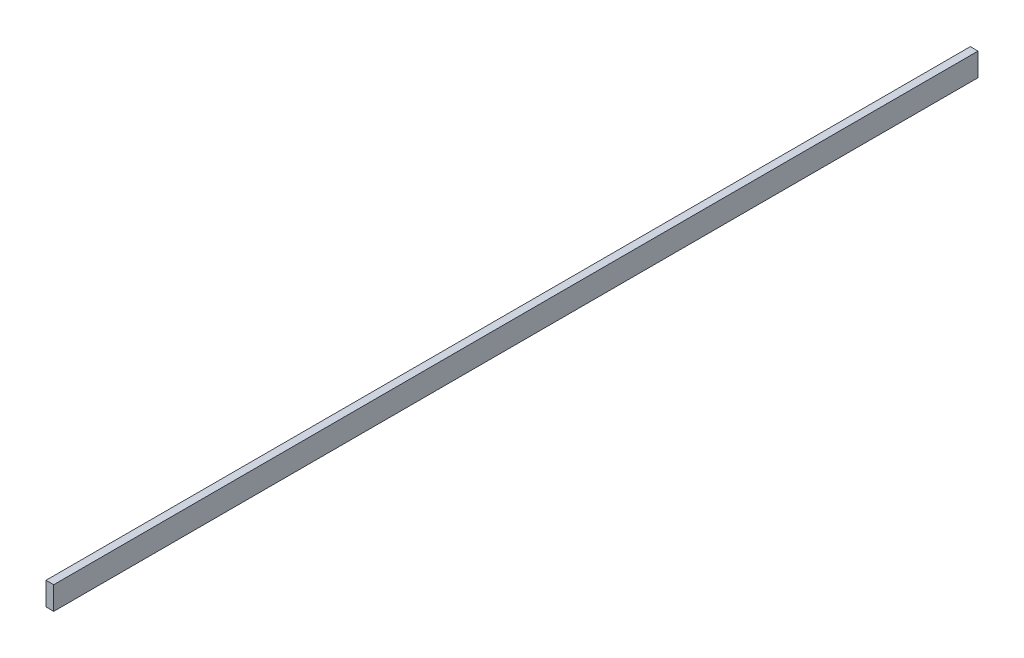
SolidWorks part; units mm, degrees
ref_plane "Front" through (0, 0, 0) normal (0, 0, 1) x (1, 0, 0)
ref_plane "Top" through (0, 0, 0) normal (0, 1, 0) x (1, 0, 0)
ref_plane "Right" through (0, 0, 0) normal (1, 0, 0) x (0, 0, -1)
sketch "Esquisse1" plane through (0, 0, 0) normal (0, 0, 1) x (1, 0, 0)
  line L1 (0, 0) -> (50, 0)
  line L2 (0, 0) -> (0, 150)
  line L3 (0, 150) -> (50, 150)
  line L4 (50, 0) -> (50, 150)
  dimension "D1" = 50
  dimension "D2" = 150
extrude "Boss.-Extru.1" add sketch "Esquisse1" along normal blind 6000
